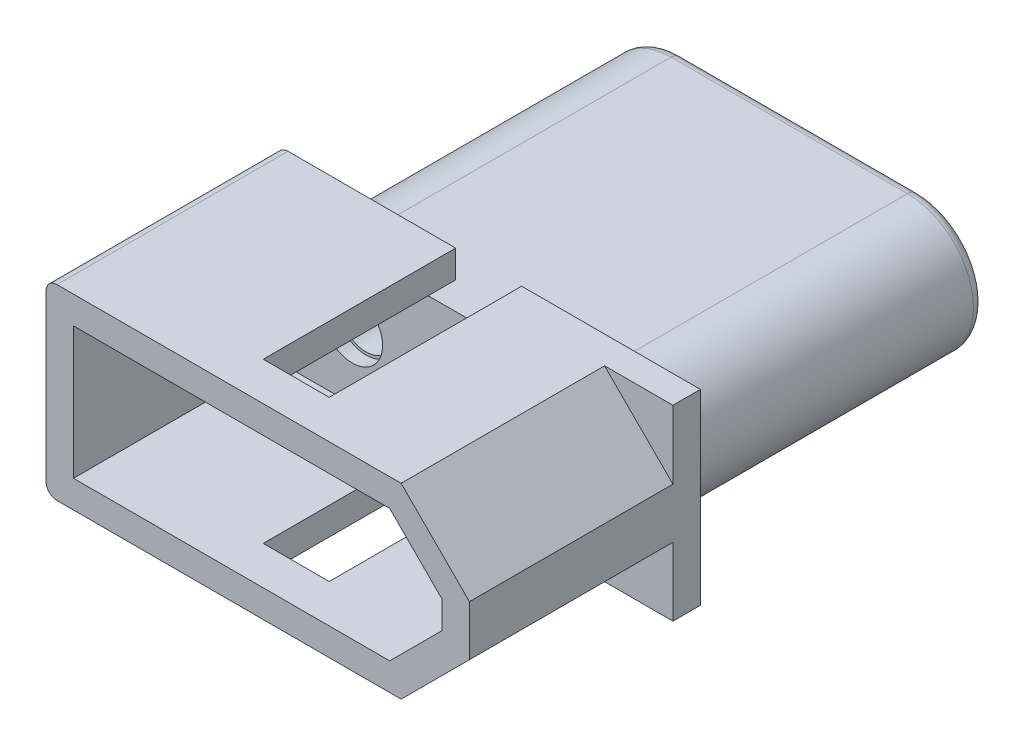
SolidWorks part; units mm, degrees
ref_plane "Front Plane" through (0, 0, 0) normal (0, 0, 1) x (1, 0, 0)
ref_plane "Top Plane" through (0, 0, 0) normal (0, 1, 0) x (1, 0, 0)
ref_plane "Right Plane" through (0, 0, 0) normal (1, 0, 0) x (0, 0, -1)
sketch "Sketch1" plane through (0, 0, 0) normal (0, 0, 1) x (1, 0, 0)
  line L0 (6.6221, 4.318) -> (-9.271, 4.318)
  line L1 (-9.779, 3.81) -> (-9.779, -3.81)
  line L2 (-9.271, -4.318) -> (6.6221, -4.318)
  line L3 (6.6221, -4.318) -> (9.779, -1.1611)
  line L4 (9.779, -1.1611) -> (9.779, 1.1611)
  line L5 (9.779, 1.1611) -> (6.6221, 4.318)
  line L6 (-9.779, 0) -> (9.779, 0) construction
  line L7 (8.509, -0.635) -> (8.509, 0.635)
  line L8 (8.509, 0.635) -> (6.096, 3.048)
  line L9 (6.096, 3.048) -> (-8.509, 3.048)
  line L10 (-8.509, 3.048) -> (-8.509, -3.048)
  line L11 (-8.509, -3.048) -> (6.096, -3.048)
  line L12 (6.096, -3.048) -> (8.509, -0.635)
  arc A0 (-9.271, 4.318) -> (-9.779, 3.81) centre (-9.271, 3.81) ccw
  arc A1 (-9.779, -3.81) -> (-9.271, -4.318) centre (-9.271, -3.81) ccw
  arc A2 (-8.509, 3.048) -> (-8.509, 3.048) centre (-8.509, 3.048) ccw
  arc A3 (-8.509, -3.048) -> (-8.509, -3.048) centre (-8.509, -3.048) ccw
  dimension "D3" = 0.508
  dimension "D1" = 19.558
  dimension "D2" = 8.636
  dimension "D4" = 45
  dimension "D5" = 1.27
  dimension "D6" = 1.27
extrude "Boss-Extrude1" add sketch "Sketch1" against normal blind 10.668
ref_plane "Plane1" through (0, 0, -25.0571) normal (0, 0, 1) x (1, 0, 0)
sketch "Sketch2" plane through (0, 0, -25.0571) normal (0, 0, 1) x (1, 0, 0)
  line L0 (0, 3.048) -> (0, -3.048) construction
  line L1 (-5.461, 3.048) -> (5.461, 3.048)
  line L3 (-5.461, -3.048) -> (5.461, -3.048)
  line L5 (6.6221, 4.318) -> (-9.271, 4.318) construction
  line L9 (-5.0292, 0) -> (5.0292, 0) construction
  circle A0 centre (-5.0292, 0) radius 1.27
  circle A1 centre (5.0292, 0) radius 1.27
  arc A2 (-5.461, 3.048) -> (-5.461, -3.048) centre (-5.461, 0) ccw
  arc A3 (5.461, -3.048) -> (5.461, 3.048) centre (5.461, 0) ccw
  circle A4 centre (0, 0) radius 1.27
  dimension "D5" = 2.54
  dimension "D1" = 17.018
  dimension "D3" = 1.27
  dimension "D6" = 10.0584
extrude "Boss-Extrude2" add sketch "Sketch2" along normal blind 15.6591 separate body
sketch "Sketch3" plane through (0, 0, -9.398) normal (0, 0, 1) x (1, 0, 0)
  line L6 (6.6221, 4.318) -> (-9.271, 4.318)
  line L7 (-9.779, 3.81) -> (-9.779, -3.81)
  line L8 (-9.271, -4.318) -> (6.6221, -4.318)
  line L9 (6.6221, -4.318) -> (9.779, -1.1611)
  line L10 (9.779, -1.1611) -> (9.779, 1.1611)
  line L11 (9.779, 1.1611) -> (6.6221, 4.318)
  line L12 (6.6221, 4.318) -> (-9.271, 4.318)
  line L13 (-9.779, 3.81) -> (-9.779, -3.81)
  line L14 (-9.271, -4.318) -> (6.6221, -4.318)
  line L15 (6.6221, -4.318) -> (9.779, -1.1611) construction
  line L16 (9.779, -1.1611) -> (9.779, 1.1611)
  line L17 (9.779, 1.1611) -> (6.6221, 4.318) construction
  line L18 (6.6221, 4.318) -> (9.779, 4.318)
  line L19 (9.779, 4.318) -> (9.779, 1.1611)
  line L20 (5.461, 3.048) -> (-5.461, 3.048)
  line L21 (-5.461, -3.048) -> (5.461, -3.048)
  line L22 (5.461, 3.048) -> (-5.461, 3.048)
  line L23 (-5.461, -3.048) -> (5.461, -3.048)
  line L24 (9.779, -1.1611) -> (9.779, -4.318)
  line L25 (9.779, -4.318) -> (6.6221, -4.318)
  arc A2 (-9.271, 4.318) -> (-9.779, 3.81) centre (-9.271, 3.81) ccw
  arc A3 (-9.779, -3.81) -> (-9.271, -4.318) centre (-9.271, -3.81) ccw
  arc A4 (-9.271, 4.318) -> (-9.779, 3.81) centre (-9.271, 3.81) ccw
  arc A5 (-9.779, -3.81) -> (-9.271, -4.318) centre (-9.271, -3.81) ccw
  arc A12 (5.461, -3.048) -> (5.461, 3.048) centre (5.461, 0) ccw
  arc A13 (-5.461, 3.048) -> (-5.461, -3.048) centre (-5.461, 0) ccw
  arc A14 (5.461, -3.048) -> (5.461, 3.048) centre (5.461, 0) ccw
  arc A15 (-5.461, 3.048) -> (-5.461, -3.048) centre (-5.461, 0) ccw
  dimension "D1" = 0
  dimension "D5" = 0
extrude "Boss-Extrude3" add sketch "Sketch3" against normal up to surface (1.27 mm away) up to face at (2.032, 0, -10.668)
sketch "Sketch4" plane through (0, 0, -25.0571) normal (0, 0, -1) x (-1, 0, 0)
  circle A0 centre (-5.0292, 0) radius 1.397
  circle A1 centre (5.0292, 0) radius 1.397
  circle A2 centre (0, 0) radius 1.397
  dimension "D1" = 2.794
extrude "Cut-Extrude1" cut sketch "Sketch4" against normal blind 0.635
sketch "Sketch5" plane through (0, 0, -9.398) normal (0, 0, 1) x (1, 0, 0)
  circle A1 centre (0, 0) radius 1.397
  circle A2 centre (0, 0) radius 1.397
  circle A3 centre (-5.0292, 0) radius 1.397
  circle A4 centre (-5.0292, 0) radius 1.397
  circle A5 centre (5.0292, 0) radius 1.397
  circle A6 centre (5.0292, 0) radius 1.397
  dimension "D1" = 0
  dimension "D2" = 0
  dimension "D3" = 0
extrude "Cut-Extrude2" cut sketch "Sketch5" against normal blind 0.635
sketch "Sketch6" plane through (0, 0, -10.668) normal (0, 0, -1) x (-1, 0, 0)
  line L0 (-9.779, 4.318) -> (9.271, 4.318) construction
  line L1 (-1.524, 4.318) -> (1.524, 4.318)
  line L2 (-1.524, 4.318) -> (-1.524, 3.048)
  line L3 (-1.524, 3.048) -> (1.524, 3.048)
  line L4 (1.524, 4.318) -> (1.524, 3.048)
  line L5 (9.271, -4.318) -> (-9.779, -4.318) construction
  line L6 (-1.524, -3.048) -> (1.524, -3.048)
  line L7 (-1.524, -3.048) -> (-1.524, -4.318)
  line L8 (-1.524, -4.318) -> (1.524, -4.318)
  line L9 (1.524, -3.048) -> (1.524, -4.318)
  line L10 (-5.461, 3.048) -> (5.461, 3.048) construction
  line L11 (5.461, -3.048) -> (-5.461, -3.048) construction
  line L12 (9.779, 3.81) -> (9.779, -3.81) construction
  dimension "D1" = 8.255
  dimension "D2" = 3.048
extrude "Cut-Extrude3" cut sketch "Sketch6" against normal blind 8.89
fillet "Fillet1" radius 0.508 4 edges at (8.509, 0, -25.0571) (0, -3.048, -25.0571) (-8.509, 0, -25.0571) (0, 3.048, -25.0571)
sketch "SketchX" plane through (0, 0, 0) normal (1, 0, 0) x (0, 0, -1)
  line L0 (25.0571, 4.9454) -> (25.0571, -4.9454) construction
  line L1 (-8.2169, 3.048) -> (0, 3.048)
  line L2 (-8.2169, 3.048) -> (-8.2169, -3.048)
  line L3 (-8.2169, -3.048) -> (0, -3.048)
  line L4 (0, 3.048) -> (0, -3.048)
  dimension "D1" = 6.096
  dimension "D2" = 33.274
